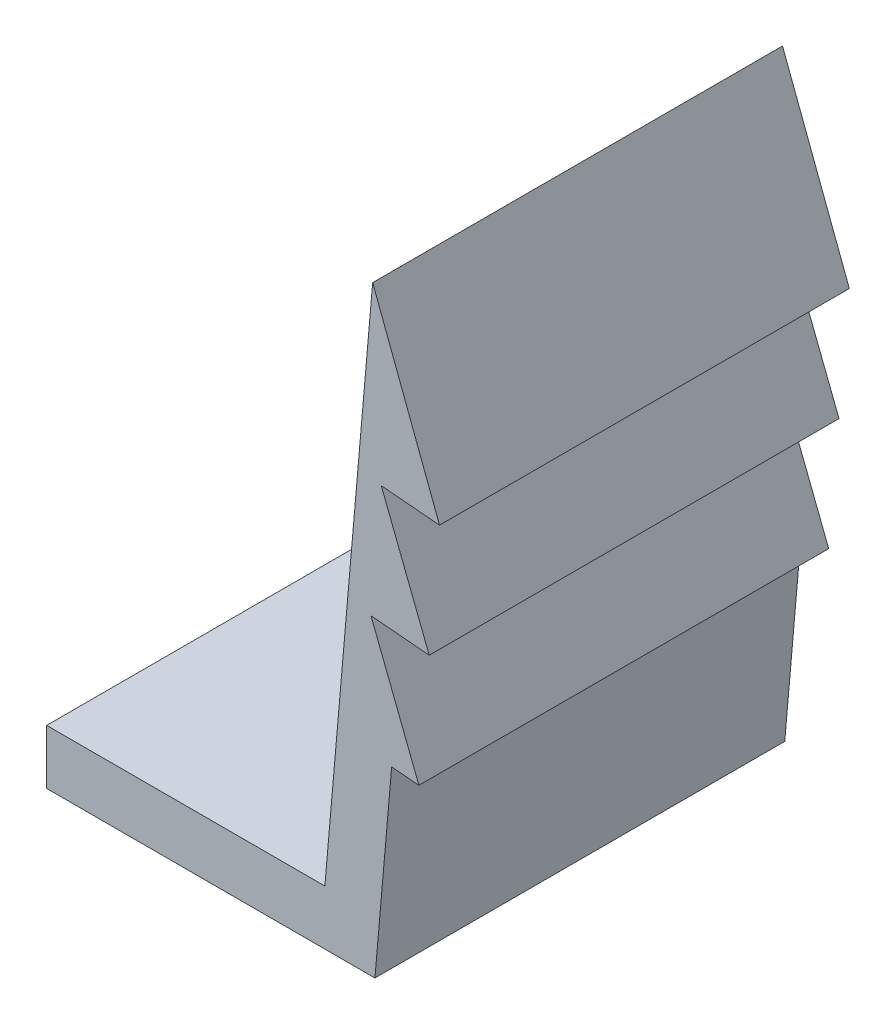
SolidWorks part; units mm, degrees
ref_plane "Front Plane" through (0, 0, 0) normal (0, 0, 1) x (1, 0, 0)
ref_plane "Top Plane" through (0, 0, 0) normal (0, 1, 0) x (1, 0, 0)
ref_plane "Right Plane" through (0, 0, 0) normal (1, 0, 0) x (0, 0, -1)
sketch "Sketch1" plane through (0, 0, 0) normal (0, 0, 1) x (1, 0, 0)
  line L0 (0, 0) -> (12.0144, 0)
  line L1 (12.0144, 0) -> (12.6268, 7)
  line L2 (12.6268, 7) -> (13.623, 6.9128)
  line L3 (13.623, 6.9128) -> (11.869, 11.4103)
  line L4 (11.869, 11.4103) -> (14.0002, 11.2239)
  line L5 (14.0002, 11.2239) -> (12.2462, 15.7214)
  line L6 (12.2462, 15.7214) -> (14.3773, 15.5349)
  line L7 (14.3773, 15.5349) -> (11.9315, 22)
  line L8 (11.9315, 22) -> (10.1817, 2)
  line L9 (10.1817, 2) -> (0, 2)
  line L10 (0, 2) -> (0, 0)
  point P3 (0, 0)
  point P13 (0, 0)
  dimension "D1" = 95
  dimension "D2" = 2
  dimension "D3" = 2
  dimension "D4" = 3
  dimension "D5" = 7
  dimension "D6" = 20
extrude "Boss-Extrude1" add sketch "Sketch1" along normal blind 15
